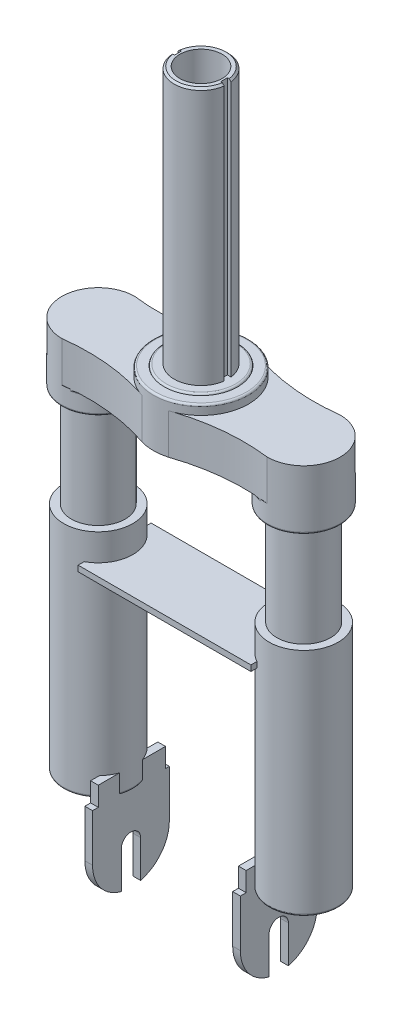
SolidWorks part; units mm, degrees
ref_plane "Front Plane" through (0, 0, 0) normal (0, 0, 1) x (1, 0, 0)
ref_plane "Top Plane" through (0, 0, 0) normal (0, 1, 0) x (1, 0, 0)
ref_plane "Right Plane" through (0, 0, 0) normal (1, 0, 0) x (0, 0, -1)
sketch "Sketch1" plane through (0, 0, 0) normal (0, 0, 1) x (1, 0, 0)
  line L0 (0, -70) -> (0, 70)
  point P4 (0, 0)
  dimension "D1" = 140
sketch "Sketch2" plane through (0, 0, 0) normal (0, 1, 0) x (1, 0, 0)
  circle A0 centre (0, 0) radius 14
  circle A1 centre (0, 0) radius 11
  dimension "D1" = 28
  dimension "D2" = 3
extrude "Boss-Extrude1" add sketch "Sketch2" against normal blind 140
sketch "Sketch3" plane through (0, -140, 0) normal (0, -1, 0) x (1, 0, 0)
  line L0 (-53.5, 0) -> (53.5, 0) construction
  line L5 (-72.5, 24.75) -> (72.5, -24.75) construction
  line L6 (-72.5, -24.75) -> (72.5, 24.75) construction
  line L7 (0, 58.8886) -> (0, -34.6433) construction
  circle A1 centre (0, 0) radius 17.2
  arc A2 (49.4574, -18.5649) -> (49.4574, 18.5649) centre (53.5, 0) ccw
  arc A3 (-49.4574, -18.5649) -> (-49.4574, 18.5649) centre (-53.5, 0) cw
  arc A4 (-8.7282, -23.1599) -> (8.7282, -23.1599) centre (0, 0) ccw
  arc A5 (-53.5, -19) -> (-6.9022, -23.7681) centre (-40.4353, -121.401) cw
  arc A6 (53.5, -19) -> (6.9022, -23.7681) centre (40.4353, -121.401) ccw
  arc A7 (53.5, 19) -> (6.9022, 23.7681) centre (40.4353, 121.401) cw
  arc A8 (-53.5, 19) -> (-6.9022, 23.7681) centre (-40.4353, 121.401) ccw
  arc A9 (8.7282, 23.1599) -> (-8.7282, 23.1599) centre (0, 0) ccw
  circle A10 centre (0, 0) radius 11 construction
  point P0 (0, 0)
  point P12 (0, 0)
  dimension "D1" = 103.231
  dimension "D3" = 34.4
  dimension "D4" = 38
  dimension "D5" = 49.5
  dimension "D2" = 6.9022
  dimension "D6" = 8.7282
  dimension "D7" = 72.5
  dimension "D8" = 24.75
  dimension "D9" = 93.5319
  dimension "D10" = 58.8886
extrude "Boss-Extrude4" add sketch "Sketch3" along normal blind 21 separate body contours A7 A9 A8 A3 A5 A4 A6 A2 A1 region at (28.6907, -140, -17.2982)
sketch "Sketch7" plane through (0, -140, 0) normal (0, 1, 0) x (1, 0, 0)
  circle A0 centre (0, 0) radius 24.75
  dimension "D1" = 49.5
extrude "Boss-Extrude5" add sketch "Sketch7" along normal blind 5
fillet "Fillet3" radius 1 1 edges at (0, -135, 24.75)
sketch "Sketch8" plane through (0, -135, 0) normal (0, 1, 0) x (1, 0, 0)
  circle A0 centre (0, 0) radius 19.15
  circle A1 centre (0, 0) radius 14 construction
  circle A2 centre (0, 0) radius 14
  dimension "D1" = 38.3
extrude "Boss-Extrude6" add sketch "Sketch8" along normal blind 0.9
fillet "Fillet4" radius 1 1 edges at (0, -134.1, 19.15)
sketch "Sketch9" plane through (0, -161, 0) normal (0, -1, 0) x (1, 0, 0)
  line L0 (-72.5, 0) -> (-53.5, 0) construction
  line L1 (0, 31.6889) -> (0, -24.75) construction
  arc A0 (-53.5, 19) -> (-53.5, -19) centre (-53.5, 0) ccw construction
  circle A1 centre (-53.5, 0) radius 19
  arc A2 (-6.9022, -23.7681) -> (6.9022, -23.7681) centre (0, 0) ccw construction
  circle A3 centre (53.5, 0) radius 19
  dimension "D1" = 38
extrude "Boss-Extrude7" add sketch "Sketch9" along normal blind 10
fillet "Fillet5" radius 1 4 edges at (34.5, -161, 0) (53.5, -171, 19) (-34.5, -161, 0) (-53.5, -171, -19)
chamfer "Chamfer1" distance 1 angle 45 1 edges at (0, 0, 14)
sketch "Sketch10" plane through (0, -171, 0) normal (0, -1, 0) x (1, 0, 0)
  line L0 (0, 39.8113) -> (0, -36.7225) construction
  circle A0 centre (-53.5, 0) radius 18 construction
  circle A1 centre (-53.5, 0) radius 18 construction
  circle A2 centre (-53.5, 0) radius 14
  circle A3 centre (53.5, 0) radius 14
  dimension "D1" = 28
extrude "Boss-Extrude8" add sketch "Sketch10" along normal blind 53
fillet "Fillet7" radius 1 2 edges at (53.5, -171, 14) (-53.5, -171, -14)
sketch "Sketch11" plane through (0, -224, 0) normal (0, -1, 0) x (1, 0, 0)
  line L0 (0, 38.6993) -> (0, -16.4417) construction
  circle A2 centre (-53.5, 0) radius 18
  circle A3 centre (-53.5, 0) radius 14 construction
  circle A4 centre (53.5, 0) radius 18
  dimension "D1" = 36
extrude "Boss-Extrude9" add sketch "Sketch11" along normal blind 120
fillet "Fillet8" radius 1 2 edges at (53.5, -344, 18) (-53.5, -344, -18)
sketch "Sketch17" plane through (0, 0, 0) normal (0, 0, 1) x (1, 0, 0)
  line L0 (-53.5, -344) -> (53.5, -344) construction
  line L1 (-70.5, -344) -> (-36.5, -344) construction
  line L2 (36.5, -344) -> (70.5, -344) construction
  line L3 (0, -344) -> (0, -319.3084) construction
  line L4 (0, -344) -> (0, -352.1369) construction
  line L5 (-36.5, -352.1369) -> (36.5, -352.1369) construction
  line L6 (36.5, -352.1369) -> (36.5, -330.8903) construction
  line L7 (-36.5, -344) -> (-36.5, -334) construction
  line L8 (-36.5, -352.1369) -> (-36.5, -337.5926)
  point P13 (0, -352.1369)
  dimension "D1" = 73
ref_plane "Plane1" through (36.5, 0, 0) normal (1, 0, 0) x (0, 0, -1)
sketch "Sketch13" plane through (36.5, 0, 0) normal (1, 0, 0) x (0, 0, -1)
  line L1 (-17, -344) -> (-17, -334) construction
  line L6 (-17, -334) -> (18, -334)
  line L17 (-17, -334) -> (18, -334) construction
  line L18 (18, -343) -> (18, -224) construction
  line L19 (-17, -344) -> (-17, -334)
  line L20 (18, -334) -> (18, -344)
  line L21 (-20, -344) -> (-17, -344)
  line L23 (-20, -344) -> (-20, -368.6338)
  line L24 (0, -344) -> (0, -388.6338) construction
  line L25 (20, -344) -> (20, -368.6338)
  line L26 (-5.02, -368.6338) -> (-5.02, -387.9936)
  line L27 (5.02, -368.6338) -> (5.02, -387.9936)
  line L28 (18, -344) -> (20, -344)
  arc A3 (5.02, -387.9936) -> (20, -368.6338) centre (0, -368.6338) ccw
  arc A4 (5.02, -368.6338) -> (-5.02, -368.6338) centre (0, -368.6338) ccw
  arc A5 (-20, -368.6338) -> (-5.02, -387.9936) centre (0, -368.6338) ccw
  point P28 (0, -344)
  dimension "D6" = 10.04
  dimension "D3" = 368.6338
  dimension "D2" = 20
  dimension "D1" = 10
extrude "Boss-Extrude14" add sketch "Sketch13" along normal blind 4
mirror "Mirror4" about plane through (0, 0, 0) normal (1, 0, 0) of "Boss-Extrude14"
sketch "Sketch20" plane through (0, 0, 0) normal (0, 0, 1) x (1, 0, 0)
  line L0 (-36.5, -387.9936) -> (0, -387.9936) construction
  line L1 (0, -387.9936) -> (0, -237.9936) construction
  line L2 (-45, -237.9936) -> (45, -237.9936)
  line L3 (-45, -237.9936) -> (-45, -240.9936)
  line L4 (45, -237.9936) -> (45, -240.9936)
  line L5 (-45, -240.9936) -> (45, -240.9936)
  point P8 (0, -237.9936)
  dimension "D1" = 150
  dimension "D2" = 90
  dimension "D3" = 3
  dimension "D4" = 3
extrude "Boss-Extrude15" add sketch "Sketch20" along normal mid plane 38
ref_plane "Plane2" through (14, 0, 0) normal (1, 0, 0) x (0, 0, -1)
sketch "Sketch21" plane through (14, 0, 0) normal (1, 0, 0) x (0, 0, -1)
  line L0 (-1.7847, -134.1) -> (1.7847, -134.1)
  line L1 (18.155, -134.1) -> (-18.155, -134.1) construction
  line L2 (-1.7847, -134.1) -> (-1.7847, 0)
  line L3 (11, 0) -> (-11, 0) construction
  line L5 (-14, -1) -> (14, -1) construction
  line L6 (1.7847, -1) -> (1.7847, -134.1)
  line L7 (1.7847, -1) -> (1.7847, 0)
  line L8 (13, 0) -> (-13, 0) construction
  line L9 (-1.7847, 0) -> (1.7847, 0)
  point P5 (0, -134.1)
  dimension "D1" = 3.5694
extrude "Cut-Extrude1" cut sketch "Sketch21" against normal blind 2
mirror "Mirror5" about plane through (0, 0, 0) normal (1, 0, 0) of "Cut-Extrude1"
